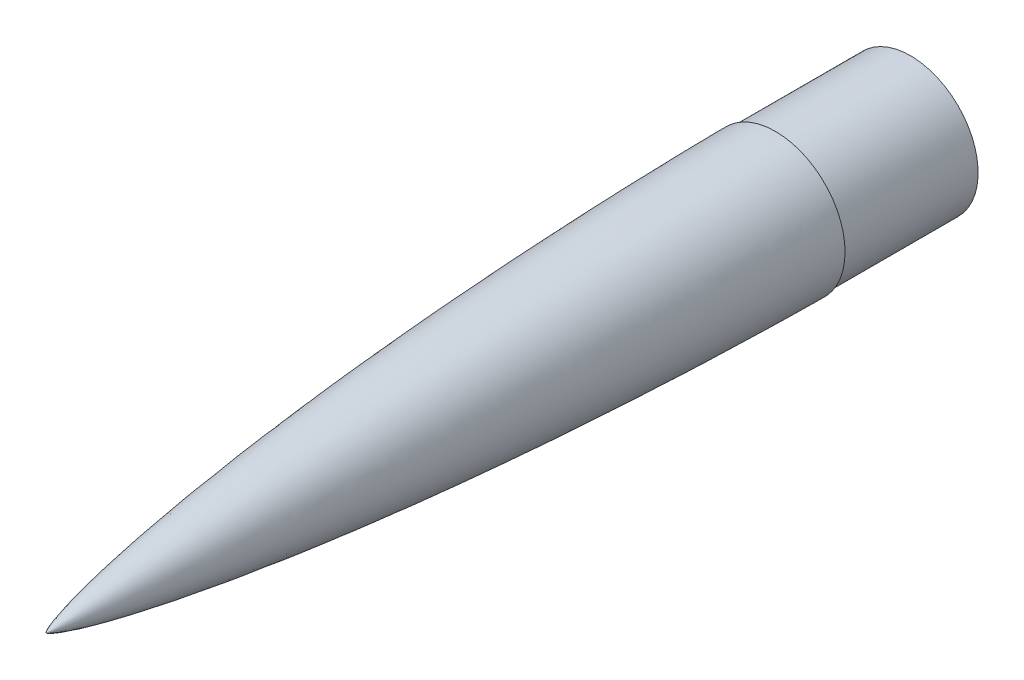
SolidWorks part; units mm, degrees
ref_plane "Front Plane" through (0, 0, 0) normal (0, 0, 1) x (1, 0, 0)
ref_plane "Top Plane" through (0, 0, 0) normal (0, 1, 0) x (1, 0, 0)
ref_plane "Right Plane" through (0, 0, 0) normal (1, 0, 0) x (0, 0, -1)
sketch "Sketch2" plane through (0, 0, 0) normal (1, 0, 0) x (0, 0, -1)
  line L2 (0, 0) -> (685.8, 0)
  line L3 (685.8, 0) -> (685.8, 65.405)
  spline S0 degree 4 poles (0, 0) (0.0025, 0.0089) (0.0093, 0.0259) (0.0295, 0.0571) (0.0636, 0.1004) (0.1077, 0.1476) (0.1715, 0.2089) (0.2498, 0.2765) (0.3425, 0.3499) (0.4498, 0.4286) (0.6199, 0.5462) (0.8271, 0.6777) (1.0716, 0.822) (1.4784, 1.047) (2.1234, 1.377) (3.293, 1.9175) (5.4483, 2.7978) (9.3183, 4.1819) (16.2109, 6.3166) (27.735, 9.3896) (47.6298, 13.9525) (76.2047, 19.5039) (112.0403, 25.4688) (153.2894, 31.4017) (195.7228, 36.7544) (238.2285, 41.4957) (280.7895, 45.7076) (323.3947, 49.4447) (366.0357, 52.7471) (408.7061, 55.6442) (446.0638, 57.844) (478.0972, 59.5006) (510.1392, 60.9782) (536.8474, 62.0623) (563.561, 63.001) (592.9512, 63.8726) (614.3287, 64.4025) (632.9927, 64.784) (648.9421, 65.0475) (658.1886, 65.1767) (666.0773, 65.2692) (672.6514, 65.3317) (677.9108, 65.3735) (681.8554, 65.3935) (684.4851, 65.405) (685.8, 65.405) knots 0 0 0 0 0 0.000053 0.000107 0.000213 0.00032 0.000426 0.000619 0.000812 0.001004 0.001197 0.001816 0.002232 0.002648 0.003889 0.00601 0.00969 0.016124 0.027679 0.047778 0.078732 0.134288 0.196196 0.258104 0.320012 0.38192 0.443828 0.505737 0.567645 0.629553 0.691461 0.722415 0.753369 0.815277 0.846231 0.877185 0.923616 0.939093 0.95432 0.969547 0.97716 0.984773 0.992387 1 1 1 1 1 construction
  spline S1 degree 4 poles (0, 0) (0.0025, 0.0089) (0.0093, 0.0259) (0.0295, 0.0571) (0.0636, 0.1004) (0.1077, 0.1476) (0.1715, 0.2089) (0.2498, 0.2765) (0.3425, 0.3499) (0.4498, 0.4286) (0.6199, 0.5462) (0.8271, 0.6777) (1.0716, 0.822) (1.4784, 1.047) (2.1234, 1.377) (3.293, 1.9175) (5.4483, 2.7978) (9.3183, 4.1819) (16.2109, 6.3166) (27.735, 9.3896) (47.6298, 13.9525) (76.2047, 19.5039) (112.0403, 25.4688) (153.2894, 31.4017) (195.7228, 36.7544) (238.2285, 41.4957) (280.7895, 45.7076) (323.3947, 49.4447) (366.0357, 52.7471) (408.7061, 55.6442) (446.0638, 57.844) (478.0972, 59.5006) (510.1392, 60.9782) (536.8474, 62.0623) (563.561, 63.001) (592.9512, 63.8726) (614.3287, 64.4025) (632.9927, 64.784) (648.9421, 65.0475) (658.1886, 65.1767) (666.0773, 65.2692) (672.6514, 65.3317) (677.9108, 65.3735) (681.8554, 65.3935) (684.4851, 65.405) (685.8, 65.405) knots 0 0 0 0 0 0.000053 0.000107 0.000213 0.00032 0.000426 0.000619 0.000812 0.001004 0.001197 0.001816 0.002232 0.002648 0.003889 0.00601 0.00969 0.016124 0.027679 0.047778 0.078732 0.134288 0.196196 0.258104 0.320012 0.38192 0.443828 0.505737 0.567645 0.629553 0.691461 0.722415 0.753369 0.815277 0.846231 0.877185 0.923616 0.939093 0.95432 0.969547 0.97716 0.984773 0.992387 1 1 1 1 1
  dimension "D1" = 65.405
  dimension "D2" = 685.8
revolve "Revolve1" add sketch "Sketch2" angle 360 about L2
shell "Shell1" thickness 1.905 removed face at (65.405, 0, -685.8)
sketch "Sketch3" plane through (0, 0, -685.8) normal (0, 0, -1) x (-1, 0, 0)
  circle A0 centre (0, 0) radius 63.5 construction
  circle A1 centre (0, 0) radius 63.5
  circle A2 centre (0, 0) radius 61.976
  dimension "D1" = 123.952
extrude "Boss-Extrude1" add sketch "Sketch3" along normal blind 127 and the other way up to next
equation "\"AIRFRAME_OD\"= 5.15in"
equation "\"AIRFRAME_ID\"= 5.00in"
equation "\"FLAT_T\"= 0.125in"
equation "\"NOSE_EXP_L\"= 27in"
equation "\"NOSE_SHOULDER_L\"= 5in"
equation "\"MAIN_L\"= 30in"
equation "\"RECO_COUP_L\"= 10in"
equation "\"RECO_SWITCH_L\"= 2in"
equation "\"DROGUE_L\"= 20in"
equation "\"ATS_FORE_COUP_L\"= 5.5in"
equation "\"ATS_AFT_COUP_L\"= 4.5in"
equation "\"LOWER_L\"= 30in"
equation "\"FIN_N\"= 4"
equation "\"CR_AFT_X\"= 0.5in"
equation "\"CR_FORE_X\"= 9.25in"
equation "\"COUPLER_OD\"= 4.998in"
equation "\"COUPLER_ID\"= 4.88in"
equation "\"RECO_ROD_X\"= 3.5in"
equation "\"ATS_ROD_X\"= 3.75in"
equation "\"FIN_ROOT\"= 8in"
equation "\"FIN_X\"= 0.75in"
equation "\"MOTOR_OD\"= 3.091in"
equation "\"MOTOR_ID\"= 3.00in"
equation "\"MOTOR_L\"= 14in"
equation "\"MOTOR_LOWER_X\"= 2in"
equation "\"NOSE_CONE_L\"=14.5in"
equation "\"D1@Shell1\"=(\"AIRFRAME_OD\"-\"AIRFRAME_ID\")/2"
equation "\"D1@Boss-Extrude1\"= \"NOSE_SHOULDER_L\""
equation "\"D1@Sketch2\"=\"AIRFRAME_OD\"/2"
equation "\"D1@Sketch3\"=\"COUPLER_ID\""
